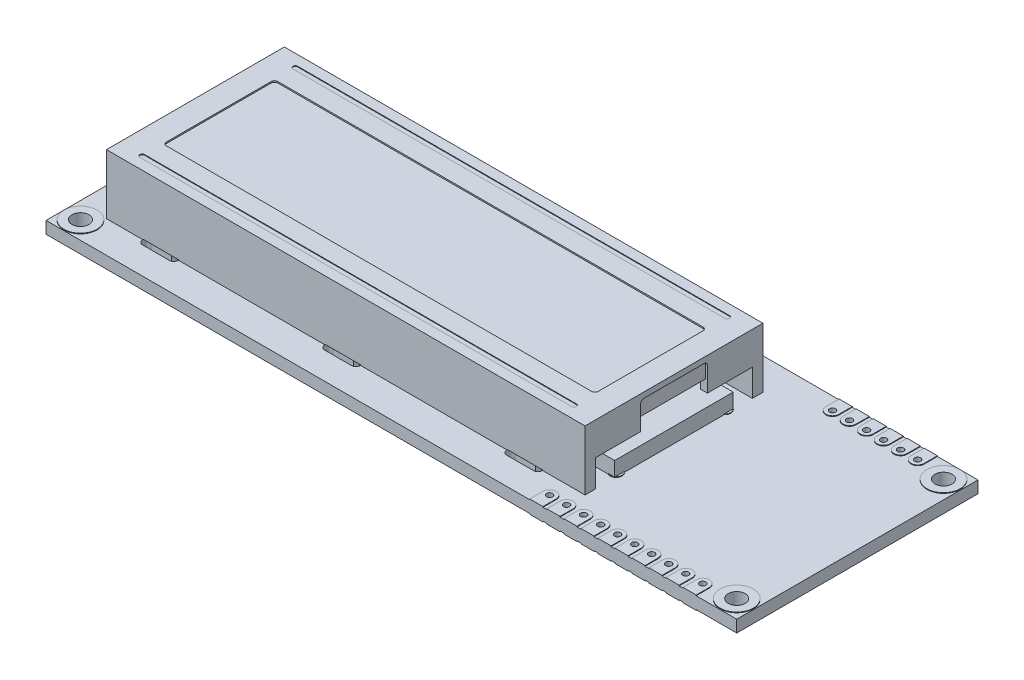
SolidWorks part; units mm, degrees
ref_plane "Front Plane" through (0, 0, 0) normal (0, 0, 1) x (1, 0, 0)
ref_plane "Top Plane" through (0, 0, 0) normal (0, 1, 0) x (1, 0, 0)
ref_plane "Right Plane" through (0, 0, 0) normal (1, 0, 0) x (0, 0, -1)
sketch "Sketch1" plane through (0, 0, 0) normal (0, 1, 0) x (1, 0, 0)
  line L5 (4.2965, 31.2697) -> (75.7035, 31.2697)
  line L6 (4.2965, 31.2697) -> (4.2965, 4.7303)
  line L7 (4.2965, 4.7303) -> (75.7035, 4.7303)
  line L8 (75.7035, 31.2697) -> (75.7035, 4.7303)
  line L9 (4.2965, 31.2697) -> (75.7035, 4.7303) construction
  line L10 (4.2965, 4.7303) -> (75.7035, 31.2697) construction
  point P5 (40, 18)
  dimension "D1" = 71.407
extrude "Boss-Extrude2" add sketch "Sketch1" along normal blind 8.93 from offset 1.79
sketch "Sketch3" plane through (0, 0, 0) normal (0, 1, 0) x (1, 0, 0)
  line L3 (40, 36) -> (103.07, 36)
  line L5 (0, 0) -> (103.07, 0)
  line L6 (0, 0) -> (0, 36)
  line L7 (0, 36) -> (103.07, 36)
  line L8 (103.07, 0) -> (103.07, 36)
  line L9 (0, 0) -> (103.07, 36) construction
  line L10 (0, 36) -> (103.07, 0) construction
  dimension "D1" = 103.07
extrude "Boss-Extrude3" add sketch "Sketch3" along normal blind 1.79 contours L5 L8 L3 L7 L6 region at (51.535, 0, -18)
sketch "Sketch4" plane through (0, 0, 0) normal (0, 1, 0) x (1, 0, 0)
  line L5 (7.78, 9.685) -> (72.22, 9.685)
  line L6 (7.78, 9.685) -> (7.78, 26.315)
  line L7 (7.78, 26.315) -> (72.22, 26.315)
  line L8 (72.22, 9.685) -> (72.22, 26.315)
  line L9 (7.78, 9.685) -> (72.22, 26.315) construction
  line L10 (7.78, 26.315) -> (72.22, 9.685) construction
extrude "Cut-Extrude1" cut sketch "Sketch4" against normal blind 0.2 from surface starting at face at (40, 10.72, -18)
ref_plane "Plane1" through (0, 10.72, 0) normal (0, 1, 0) x (1, 0, 0)
sketch "Sketch6" plane through (0, 10.72, 0) normal (0, 1, 0) x (1, 0, 0)
  line L4 (7.78, 29.7697) -> (72.22, 29.7697)
  line L5 (7.78, 29.0648) -> (72.22, 29.0648)
  circle A0 centre (7.78, 29.4173) radius 0.3524
  circle A1 centre (72.22, 29.4173) radius 0.3524
extrude "Cut-Extrude4" cut sketch "Sketch6" against normal blind 0.1 contours A1 L4 A0 L5 | A1 | A0 region at (40, 10.72, -29.4173) region at (7.78, 10.72, -29.4173) region at (72.22, 10.72, -29.4173)
ref_plane "Plane2" through (0, 0, -18) normal (0, 0, 1) x (1, 0, 0)
mirror "Mirror1" about plane through (0, 0, -18) normal (0, 0, 1) of "Cut-Extrude4"
fillet "Fillet1" radius 0.5 4 edges at (72.22, 10.62, -9.685) (72.22, 10.62, -26.315) (7.78, 10.62, -9.685) (7.78, 10.62, -26.315)
sketch "Sketch7" plane through (0, 0, 0) normal (1, 0, 0) x (0, 0, -1)
  line L5 (6.3, 1.79) -> (29.7, 1.79)
  line L6 (6.3, 1.79) -> (6.3, 5.83)
  line L7 (6.3, 5.83) -> (29.7, 5.83)
  line L8 (29.7, 1.79) -> (29.7, 5.83)
  line L9 (6.3, 1.79) -> (29.7, 5.83) construction
  line L10 (6.3, 5.83) -> (29.7, 1.79) construction
  point P6 (18, 3.81)
extrude "Cut-Extrude5" cut sketch "Sketch7" along normal through all contours L5 L8 L7 L6 region at (0, 3.81, -18)
ref_plane "Plane3" through (4.2965, 0, 0) normal (-1, 0, 0) x (0, 0, 1)
sketch "Sketch8" plane through (4.2965, 0, 0) normal (-1, 0, 0) x (0, 0, 1)
  line L2 (0, 1.79) -> (-36, 1.79) construction
  line L6 (-26.84, 1.79) -> (-9.155, 1.79)
  line L7 (-26.84, 1.79) -> (-26.84, 4.04)
  line L8 (-26.84, 4.04) -> (-9.155, 4.04)
  line L9 (-9.155, 1.79) -> (-9.155, 4.04)
extrude "Boss-Extrude5" add sketch "Sketch8" against normal blind 69.41 from offset 2 offset against normal yes
sketch "Sketch13" plane through (0, 4.04, 0) normal (0, 1, 0) x (1, 0, 0)
  line L0 (6.2965, 26.84) -> (6.2965, 9.155)
  line L2 (1.5, 20.9275) -> (6.2965, 26.84)
  line L5 (1.5, 20.9275) -> (1.5, 15.0675)
  line L8 (1.5, 15.0675) -> (6.2965, 9.155)
extrude "Boss-Extrude6" add sketch "Sketch13" against normal up to next
ref_plane "Plane5" through (75.7035, 0, 0) normal (1, 0, 0) x (0, 0, -1)
sketch "Sketch14" plane through (75.7035, 0, 0) normal (1, 0, 0) x (0, 0, -1)
  line L2 (18, 6.996) -> (18, -6.996) construction
  line L3 (18, 9.9) -> (13.02, 9.9)
  line L4 (18, 9.9) -> (22.98, 9.9)
  line L6 (13.02, 9.9) -> (22.98, 9.9)
  line L7 (13.02, 9.9) -> (13.02, 5.83)
  line L8 (13.02, 5.83) -> (22.98, 5.83)
  line L9 (22.98, 9.9) -> (22.98, 5.83)
extrude "Cut-Extrude6" cut sketch "Sketch14" against normal blind 0.3 contours L9 L4 L3 L7 L8 region at (75.7035, 7.865, -18)
fillet "Fillet2" radius 0.5 2 edges at (75.5535, 9.9, -22.98) (75.5535, 9.9, -13.02)
sketch "Sketch15" plane through (75.4035, 0, 0) normal (1, 0, 0) x (0, 0, -1)
  line L1 (13.02, 9.4) -> (13.02, 5.83) construction
  line L3 (13.02, 7.5) -> (22.98, 7.5)
  line L4 (13.02, 7.5) -> (13.02, 5.83)
  line L5 (13.02, 5.83) -> (22.98, 5.83)
  line L6 (22.98, 7.5) -> (22.98, 5.83)
extrude "Cut-Extrude7" cut sketch "Sketch15" against normal blind 70.4
sketch "Sketch18" plane through (75.7035, 0, 0) normal (1, 0, 0) x (0, 0, -1)
  line L2 (13.02, 9.4) -> (13.02, 5.83) construction
  line L3 (6.3, 7.5) -> (13.02, 7.5)
  line L4 (6.3, 7.5) -> (6.3, 5.83)
  line L5 (6.3, 5.83) -> (13.02, 5.83)
  line L6 (13.02, 7.5) -> (13.02, 5.83)
  line L7 (6.3, 5.83) -> (13.02, 5.83) construction
  line L8 (22.98, 5.83) -> (29.7, 5.83) construction
  line L9 (29.7, 7.5) -> (22.98, 7.5)
  line L10 (29.7, 7.5) -> (29.7, 5.83)
  line L11 (29.7, 5.83) -> (22.98, 5.83)
  line L12 (22.98, 7.5) -> (22.98, 5.83)
  line L13 (22.98, 9.4) -> (22.98, 5.83) construction
extrude "Cut-Extrude8" cut sketch "Sketch18" against normal blind 68.4 from offset 1 offset against normal yes
sketch "Sketch20" plane through (0, 0, 0) normal (0, 1, 0) x (1, 0, 0)
  circle A0 centre (2.57, 33.43) radius 2.475
  circle A1 centre (100.4939, 33.43) radius 2.475
  circle A2 centre (2.57, 2.57) radius 2.475
  circle A3 centre (100.4939, 2.57) radius 2.475
extrude "Boss-Extrude7" add sketch "Sketch20" along normal blind 1.99 from offset 0.1 offset against normal yes
sketch "Sketch23" plane through (0, 0, 0) normal (0, 1, 0) x (1, 0, 0)
  circle A0 centre (2.57, 33.43) radius 1.27
  circle A1 centre (100.4939, 33.43) radius 1.27
  circle A2 centre (2.57, 2.57) radius 1.27
  circle A3 centre (100.4939, 2.57) radius 1.27
extrude "Cut-Extrude10" cut sketch "Sketch23" against normal through all both and the other way through all
sketch "Sketch24" plane through (0, 0, 0) normal (0, 1, 0) x (1, 0, 0)
  line L0 (103.07, 0) -> (75.11, 0)
  line L4 (1.5, 15.0675) -> (1.5, 20.9275) construction
  line L5 (103.07, 0) -> (103.07, 36) construction
  line L6 (0, 0) -> (103.07, 0) construction
  line L9 (0.3, 16.1022) -> (1.5, 16.1022)
  line L10 (0.3, 16.1022) -> (0.3, 17.3067)
  line L11 (0.3, 17.3067) -> (1.5, 17.3067)
  line L12 (1.5, 16.1022) -> (1.5, 17.3067)
  line L13 (0.3, 16.1022) -> (1.5, 17.3067) construction
  line L14 (0.3, 17.3067) -> (1.5, 16.1022) construction
  circle A0 centre (0.9, 10.6) radius 0.9
  circle A1 centre (0.9, 14.2) radius 0.9
  circle A2 centre (0.9, 25.72) radius 0.9
  circle A3 centre (0.9, 21.88) radius 0.9
  circle A4 centre (0.9, 19.2833) radius 0.6
  circle A5 centre (4.85, 26.17) radius 0.9
  circle A6 centre (4.85, 9.95) radius 0.9
  circle A7 centre (75.11, 9.95) radius 0.9
  circle A8 centre (75.11, 26.17) radius 0.9
  point P22 (0.9, 16.7044)
extrude "Boss-Extrude16" add sketch "Sketch24" along normal blind 1.99 from offset 0.1 separate body contours A3 | A4 | L9 L12 L11 L10 | A1 | A6 | A0 | A7 | A8 | A2 | A5 region at (0.9, 0, -16.7044) region at (0.9, 0, -10.6) region at (0.9, 0, -14.2) region at (0.9, 0, -25.72) region at (0.9, 0, -21.88) region at (0.9, 0, -19.2833) region at (4.85, 0, -26.17) region at (4.85, 0, -9.95) region at (75.11, 0, -9.95) region at (75.11, 0, -26.17) offset against normal yes
sketch "Sketch26" plane through (0, 0, 0) normal (0, 1, 0) x (1, 0, 0)
  circle A0 centre (0.9, 25.72) radius 0.54
  circle A1 centre (0.9, 21.88) radius 0.54
  circle A2 centre (0.9, 19.2833) radius 0.45
  circle A3 centre (0.9, 16.7044) radius 0.45
  circle A4 centre (0.9, 14.2) radius 0.54
  circle A5 centre (0.9, 10.6) radius 0.54
  circle A7 centre (4.85, 9.95) radius 0.54
  circle A9 centre (4.85, 26.17) radius 0.54
  circle A11 centre (75.11, 26.17) radius 0.54
  circle A13 centre (75.11, 9.95) radius 0.54
extrude "Cut-Extrude11" cut sketch "Sketch26" along normal blind 1.99 from offset 0.1 contours A0 | A9 | A1 | A2 | A4 | A5 | A7 | A13 | A3 | A11 region at (0.9, 0, -25.72) region at (0.9, 0, -21.88) region at (0.9, 0, -19.2833) region at (0.9, 0, -14.2) region at (0.9, 0, -10.6) region at (4.85, 0, -9.95) region at (4.85, 0, -26.17) region at (75.11, 0, -9.95) offset against normal yes
sketch "Sketch27" plane through (0, 0, 0) normal (0, 1, 0) x (1, 0, 0)
  line L0 (95.0478, 34.03) -> (95.0478, 36)
  line L2 (97.014, 0) -> (95.0478, 0)
  line L3 (95.0478, 0) -> (95.0478, 1.97)
  line L4 (0, 36) -> (103.07, 36) construction
  line L5 (97.014, 1.97) -> (97.014, 0)
  line L6 (92.5078, 0) -> (92.5078, 1.97)
  line L7 (94.474, 1.97) -> (94.474, 0)
  line L8 (94.474, 0) -> (92.5078, 0)
  line L9 (89.9678, 0) -> (89.9678, 1.97)
  line L10 (91.934, 1.97) -> (91.934, 0)
  line L11 (91.934, 0) -> (89.9678, 0)
  line L12 (87.4278, 0) -> (87.4278, 1.97)
  line L13 (89.394, 1.97) -> (89.394, 0)
  line L14 (89.394, 0) -> (87.4278, 0)
  line L15 (84.8878, 0) -> (84.8878, 1.97)
  line L16 (86.854, 1.97) -> (86.854, 0)
  line L17 (86.854, 0) -> (84.8878, 0)
  line L18 (82.3478, 0) -> (82.3478, 1.97)
  line L19 (84.314, 1.97) -> (84.314, 0)
  line L20 (84.314, 0) -> (82.3478, 0)
  line L21 (79.8078, 0) -> (79.8078, 1.97)
  line L22 (81.774, 1.97) -> (81.774, 0)
  line L23 (81.774, 0) -> (79.8078, 0)
  line L24 (77.2678, 0) -> (77.2678, 1.97)
  line L25 (79.234, 1.97) -> (79.234, 0)
  line L26 (79.234, 0) -> (77.2678, 0)
  line L27 (74.7278, 0) -> (74.7278, 1.97)
  line L28 (76.694, 1.97) -> (76.694, 0)
  line L29 (76.694, 0) -> (74.7278, 0)
  line L30 (72.1878, 0) -> (72.1878, 1.97)
  line L31 (74.154, 1.97) -> (74.154, 0)
  line L32 (74.154, 0) -> (72.1878, 0)
  line L33 (95.0478, 36) -> (97.014, 36)
  line L34 (97.014, 36) -> (97.014, 34.03)
  line L35 (95.0478, 34.03) -> (97.014, 34.03)
  line L39 (94.474, 36) -> (94.474, 34.03)
  line L40 (94.474, 36) -> (92.5078, 36)
  line L41 (92.5078, 36) -> (92.5078, 34.03)
  line L42 (91.934, 36) -> (91.934, 34.03)
  line L43 (91.934, 36) -> (89.9678, 36)
  line L44 (89.9678, 36) -> (89.9678, 34.03)
  line L45 (89.394, 36) -> (89.394, 34.03)
  line L46 (89.394, 36) -> (87.4278, 36)
  line L47 (87.4278, 36) -> (87.4278, 34.03)
  line L48 (86.854, 36) -> (86.854, 34.03)
  line L49 (86.854, 36) -> (84.8878, 36)
  line L50 (84.8878, 36) -> (84.8878, 34.03)
  line L51 (58.914, 1.97) -> (58.914, 0) [skipped]
  line L52 (56.9478, 0) -> (56.9478, 1.97) [skipped]
  line L53 (58.914, 0) -> (56.9478, 0) [skipped]
  line L54 (61.454, 1.97) -> (61.454, 0) [skipped]
  line L55 (59.4878, 0) -> (59.4878, 1.97) [skipped]
  line L56 (61.454, 0) -> (59.4878, 0) [skipped]
  line L57 (62.0278, 0) -> (62.0278, 1.97) [skipped]
  line L58 (63.994, 1.97) -> (63.994, 0) [skipped]
  line L59 (63.994, 0) -> (62.0278, 0) [skipped]
  line L60 (64.5678, 0) -> (64.5678, 1.97) [skipped]
  line L61 (66.534, 1.97) -> (66.534, 0) [skipped]
  line L62 (66.534, 0) -> (64.5678, 0) [skipped]
  line L63 (67.1078, 0) -> (67.1078, 1.97) [skipped]
  line L64 (69.074, 1.97) -> (69.074, 0) [skipped]
  line L65 (69.074, 0) -> (67.1078, 0) [skipped]
  line L66 (69.6478, 0) -> (69.6478, 1.97) [skipped]
  line L67 (71.614, 1.97) -> (71.614, 0) [skipped]
  line L68 (71.614, 0) -> (69.6478, 0) [skipped]
  line L69 (84.314, 36) -> (84.314, 34.03)
  line L70 (84.314, 36) -> (82.3478, 36)
  line L71 (82.3478, 36) -> (82.3478, 34.03)
  circle A0 centre (96.0309, 1.97) radius 0.9831
  circle A1 centre (93.4909, 1.97) radius 0.9831
  circle A2 centre (90.9509, 1.97) radius 0.9831
  circle A3 centre (88.4109, 1.97) radius 0.9831
  circle A4 centre (85.8709, 1.97) radius 0.9831
  circle A5 centre (83.3309, 1.97) radius 0.9831
  circle A6 centre (80.7909, 1.97) radius 0.9831
  circle A7 centre (78.2509, 1.97) radius 0.9831
  circle A8 centre (75.7109, 1.97) radius 0.9831
  circle A9 centre (73.1709, 1.97) radius 0.9831
  circle A10 centre (96.0309, 34.03) radius 0.9831
  circle A11 centre (93.4909, 34.03) radius 0.9831
  circle A12 centre (90.9509, 34.03) radius 0.9831
  circle A13 centre (88.4109, 34.03) radius 0.9831
  circle A14 centre (85.8709, 34.03) radius 0.9831
  circle A15 centre (83.3309, 34.03) radius 0.9831
  circle A16 centre (57.9309, 1.97) radius 0.9831 [skipped]
  circle A17 centre (60.4709, 1.97) radius 0.9831 [skipped]
  circle A18 centre (63.0109, 1.97) radius 0.9831 [skipped]
  circle A19 centre (65.5509, 1.97) radius 0.9831 [skipped]
  circle A20 centre (68.0909, 1.97) radius 0.9831 [skipped]
  circle A21 centre (70.6309, 1.97) radius 0.9831 [skipped]
  dimension "D1" = 16
extrude "Boss-Extrude17" add sketch "Sketch27" along normal blind 1.99 from offset 0.1 contours A15 | A14 | A14 | A13 | A13 | A12 | A12 | A11 | A9 L30 L32 L31 | A9 | A8 L27 L29 L28 | A8 | A7 L24 L26 L25 | A6 L21 L23 L22 | A6 | A5 | A5 L18 L20 L19 | A4 L15 L17 L16 | A3 L12 L14 L13 | A3 | A2 | A2 L9 L11 L10 | A1 L6 L8 L7 | A1 | A0 L3 L2 L5 | A7 | A10 L34 L33 L0 | A15 | A11 | A4 | A0 | A10 region at (96.0309, 0, -35.381) region at (96.0309, 0, -0.619) region at (93.4909, 0, -0.619) region at (93.4909, 0, -1.97) region at (90.9509, 0, -0.619) region at (90.9509, 0, -1.97) region at (88.4109, 0, -0.619) region at (88.4109, 0, -1.97) region at (85.8709, 0, -0.619) region at (83.3309, 0, -0.619) region at (83.3309, 0, -1.97) region at (80.7909, 0, -0.619) region at (80.7909, 0, -1.97) region at (78.2509, 0, -0.619) region at (78.2509, 0, -1.97) region at (75.7109, 0, -0.619) region at (75.7109, 0, -1.97) region at (73.1709, 0, -0.619) region at (73.1709, 0, -1.97) region at (93.4909, 0, -35.381) region at (90.9509, 0, -35.381) region at (90.9509, 0, -34.03) region at (88.4109, 0, -35.381) region at (88.4109, 0, -34.03) region at (85.8709, 0, -35.381) region at (85.8709, 0, -34.03) region at (83.3309, 0, -35.381) offset against normal yes
sketch "Sketch28" plane through (0, 0, 0) normal (0, 1, 0) x (1, 0, 0)
  circle A0 centre (93.4909, 1.97) radius 0.45
  circle A1 centre (96.0309, 1.97) radius 0.45
  circle A2 centre (90.9509, 1.97) radius 0.45
  circle A3 centre (88.4109, 1.97) radius 0.45
  circle A4 centre (85.8709, 1.97) radius 0.45
  circle A5 centre (83.3309, 1.97) radius 0.45
  circle A6 centre (80.7909, 1.97) radius 0.45
  circle A7 centre (78.2509, 1.97) radius 0.45
  circle A8 centre (75.7109, 1.97) radius 0.45
  circle A9 centre (73.1709, 1.97) radius 0.45
  circle A10 centre (96.0309, 34.03) radius 0.45
  circle A11 centre (93.4909, 34.03) radius 0.45
  circle A12 centre (90.9509, 34.03) radius 0.45
  circle A13 centre (88.4109, 34.03) radius 0.45
  circle A14 centre (85.8709, 34.03) radius 0.45
  circle A15 centre (83.3309, 34.03) radius 0.45
  circle A16 centre (70.6309, 1.97) radius 0.45 [skipped]
  circle A17 centre (68.0909, 1.97) radius 0.45 [skipped]
  circle A18 centre (65.5509, 1.97) radius 0.45 [skipped]
  circle A19 centre (63.0109, 1.97) radius 0.45 [skipped]
  circle A20 centre (60.4709, 1.97) radius 0.45 [skipped]
  circle A21 centre (57.9309, 1.97) radius 0.45 [skipped]
  point P33 (0, 0)
  dimension "D1" = 16
extrude "Cut-Extrude12" cut sketch "Sketch28" against normal through all both and the other way through all contours A8 | A7 | A6 | A5 | A4 | A3 | A2 | A0 | A1 | A15 | A14 | A12 | A11 | A10 | A9 | A13 region at (93.4909, 0, -1.97) region at (96.0309, 0, -1.97) region at (90.9509, 0, -1.97) region at (88.4109, 0, -1.97) region at (85.8709, 0, -1.97) region at (83.3309, 0, -1.97) region at (80.7909, 0, -1.97) region at (78.2509, 0, -1.97) region at (75.7109, 0, -1.97) region at (96.0309, 0, -34.03) region at (93.4909, 0, -34.03) region at (90.9509, 0, -34.03) region at (85.8709, 0, -34.03) region at (83.3309, 0, -34.03)
ref_plane "Plane6" through (0, 0, 0) normal (0, -1, 0) x (-1, 0, 0)
sketch "Sketch29" plane through (0, 0, 0) normal (0, -1, 0) x (-1, 0, 0)
  line L0 (-103.07, 36) -> (-69.36, 36)
  line L2 (-68.81, 27.3375) -> (-68.81, 25.7375)
  line L3 (-73.1, 23.05) -> (-74.7, 23.05)
  line L4 (-73.1, 23.05) -> (-73.1, 24.2)
  line L5 (-73.1, 24.2) -> (-74.7, 24.2)
  line L6 (-75.5, 23.05) -> (-77.1, 23.05)
  line L7 (-75.5, 23.05) -> (-75.5, 24.2)
  line L8 (-75.5, 24.2) -> (-77.1, 24.2)
  line L9 (-77.1, 23.05) -> (-77.1, 24.2)
  line L10 (-74.7, 23.05) -> (-74.7, 24.2)
  line L11 (-73.1, 21.1) -> (-74.7, 21.1)
  line L12 (-73.1, 21.1) -> (-73.1, 22.25)
  line L13 (-73.1, 22.25) -> (-74.7, 22.25)
  line L14 (-75.5, 21.1) -> (-77.1, 21.1)
  line L15 (-75.5, 21.1) -> (-75.5, 22.25)
  line L16 (-75.5, 22.25) -> (-77.1, 22.25)
  line L17 (-77.1, 21.1) -> (-77.1, 22.25)
  line L18 (-74.7, 21.1) -> (-74.7, 22.25)
  line L19 (-73.1, 19.15) -> (-74.7, 19.15)
  line L20 (-73.1, 19.15) -> (-73.1, 20.3)
  line L21 (-73.1, 20.3) -> (-74.7, 20.3)
  line L22 (-75.5, 19.15) -> (-77.1, 19.15)
  line L23 (-75.5, 19.15) -> (-75.5, 20.3)
  line L24 (-75.5, 20.3) -> (-77.1, 20.3)
  line L25 (-77.1, 19.15) -> (-77.1, 20.3)
  line L26 (-74.7, 19.15) -> (-74.7, 20.3)
  line L27 (-68.81, 27.3375) -> (-69.96, 27.3375)
  line L28 (-69.96, 27.3375) -> (-69.96, 25.7375)
  line L29 (-68.81, 24.9375) -> (-68.81, 23.3375)
  line L30 (-68.81, 24.9375) -> (-69.96, 24.9375)
  line L31 (-69.96, 24.9375) -> (-69.96, 23.3375)
  line L32 (-68.81, 23.3375) -> (-69.96, 23.3375)
  line L33 (-68.81, 25.7375) -> (-69.96, 25.7375)
  line L34 (0, 36) -> (-82.3478, 36) construction
  line L35 (-25.55, 21.62) -> (-27.15, 21.62)
  line L36 (-25.55, 21.62) -> (-25.55, 22.77)
  line L37 (-25.55, 22.77) -> (-27.15, 22.77)
  line L38 (-27.95, 21.62) -> (-29.55, 21.62)
  line L39 (-27.95, 21.62) -> (-27.95, 22.77)
  line L40 (-27.95, 22.77) -> (-29.55, 22.77)
  line L41 (-29.55, 21.62) -> (-29.55, 22.77)
  line L42 (-27.15, 21.62) -> (-27.15, 22.77)
  line L43 (-15.0314, 29.08) -> (-9.7371, 29.08)
  line L44 (-25.55, 19.67) -> (-27.15, 19.67)
  line L45 (-25.55, 19.67) -> (-25.55, 20.82)
  line L46 (-25.55, 20.82) -> (-27.15, 20.82)
  line L47 (-27.95, 19.67) -> (-29.55, 19.67)
  line L48 (-27.95, 19.67) -> (-27.95, 20.82)
  line L49 (-27.95, 20.82) -> (-29.55, 20.82)
  line L50 (-29.55, 19.67) -> (-29.55, 20.82)
  line L51 (-27.15, 19.67) -> (-27.15, 20.82)
  line L52 (-25.55, 17.72) -> (-27.15, 17.72)
  line L53 (-25.55, 17.72) -> (-25.55, 18.87)
  line L54 (-25.55, 18.87) -> (-27.15, 18.87)
  line L55 (-27.95, 17.72) -> (-29.55, 17.72)
  line L56 (-27.95, 17.72) -> (-27.95, 18.87)
  line L57 (-27.95, 18.87) -> (-29.55, 18.87)
  line L58 (-29.55, 17.72) -> (-29.55, 18.87)
  line L59 (-27.15, 17.72) -> (-27.15, 18.87)
  line L60 (-42.1957, 29.08) -> (-36.9014, 29.08)
  line L61 (-69.36, 29.08) -> (-64.0657, 29.08)
  line L62 (-69.36, 29.08) -> (-69.36, 30.4457)
  line L63 (-69.36, 30.4457) -> (-64.0657, 30.4457)
  line L64 (-64.0657, 29.08) -> (-64.0657, 30.4457)
  line L65 (-42.1957, 29.08) -> (-42.1957, 30.4457)
  line L66 (-42.1957, 30.4457) -> (-36.9014, 30.4457)
  line L67 (-36.9014, 29.08) -> (-36.9014, 30.4457)
  line L68 (-15.0314, 29.08) -> (-15.0314, 30.4457)
  line L69 (-15.0314, 30.4457) -> (-9.7371, 30.4457)
  line L70 (-9.7371, 29.08) -> (-9.7371, 30.4457)
  line L71 (-42.1957, 5.49) -> (-36.9014, 5.49)
  line L72 (-15.0314, 5.49) -> (-9.7371, 5.49)
  line L73 (-15.0314, 5.49) -> (-15.0314, 6.8557)
  line L74 (-15.0314, 6.8557) -> (-9.7371, 6.8557)
  line L75 (-9.7371, 5.49) -> (-9.7371, 6.8557)
  line L76 (-7.27, 21.25) -> (-7.27, 22.95)
  line L77 (-7.27, 14.07) -> (-7.27, 15.77)
  line L78 (-74.13, 14.91) -> (-75.59, 14.91)
  line L79 (-74.13, 14.91) -> (-74.13, 16.12)
  line L80 (-76.19, 14.91) -> (-77.65, 14.91)
  line L81 (-76.19, 14.91) -> (-76.19, 16.12)
  line L82 (-76.19, 16.12) -> (-77.65, 16.12)
  line L83 (-77.65, 14.91) -> (-77.65, 16.12)
  line L84 (-74.13, 16.12) -> (-75.59, 16.12)
  line L85 (-75.59, 14.91) -> (-75.59, 16.12)
  line L86 (-12.2, 13) -> (-12.2, 14.7)
  line L87 (-12.2, 13) -> (-14.2, 13)
  line L88 (-14.2, 13) -> (-14.2, 14.7)
  line L89 (-14.2, 14.7) -> (-12.2, 14.7)
  line L90 (-7.27, 14.07) -> (-9.27, 14.07)
  line L91 (-12.2, 16.2) -> (-12.2, 17.9)
  line L92 (-12.2, 16.2) -> (-14.2, 16.2)
  line L93 (-14.2, 16.2) -> (-14.2, 17.9)
  line L94 (-14.2, 17.9) -> (-12.2, 17.9)
  line L95 (-9.27, 14.07) -> (-9.27, 15.77)
  line L96 (-9.27, 15.77) -> (-7.27, 15.77)
  line L97 (-7.27, 17.27) -> (-7.27, 18.97)
  line L98 (-7.27, 17.27) -> (-9.27, 17.27)
  line L99 (-9.27, 17.27) -> (-9.27, 18.97)
  line L100 (-9.27, 18.97) -> (-7.27, 18.97)
  line L101 (-7.27, 21.25) -> (-9.27, 21.25)
  line L102 (-9.27, 21.25) -> (-9.27, 22.95)
  line L103 (-9.27, 22.95) -> (-7.27, 22.95)
  line L104 (-7.27, 24.45) -> (-7.27, 26.15)
  line L105 (-7.27, 24.45) -> (-9.27, 24.45)
  line L106 (-9.27, 24.45) -> (-9.27, 26.15)
  line L107 (-9.27, 26.15) -> (-7.27, 26.15)
  line L108 (-42.1957, 5.49) -> (-42.1957, 6.8557)
  line L109 (-42.1957, 6.8557) -> (-36.9014, 6.8557)
  line L110 (-36.9014, 5.49) -> (-36.9014, 6.8557)
  line L111 (-69.36, 5.49) -> (-64.0657, 5.49)
  line L112 (-69.36, 5.49) -> (-69.36, 6.8557)
  line L113 (-69.36, 6.8557) -> (-64.0657, 6.8557)
  line L114 (-64.0657, 5.49) -> (-64.0657, 6.8557)
  circle A0 centre (-4.85, 14.85) radius 0.99
  circle A1 centre (-4.85, 21.86) radius 0.99
extrude "Boss-Extrude18" add sketch "Sketch29" along normal blind 0.1 contours A0 | L96 L95 L90 L77 | L100 L99 L98 L97 | L94 L93 L92 L91 | L89 L88 L87 L86 | L103 L102 L101 L76 | L107 L106 L105 L104 | A1 | L43 L70 L69 L68 | L59 L52 L53 L54 | L51 L44 L45 L46 | L42 L35 L36 L37 | L41 L38 L39 L40 | L50 L47 L48 L49 | L58 L55 L56 L57 | L61 L64 L63 L62 | L33 L2 L27 L28 | L10 L3 L4 L5 | L9 L6 L7 L8 | L17 L14 L15 L16 | L18 L11 L12 L13 | L26 L19 L20 L21 | L25 L22 L23 L24 | L83 L80 L81 L82 | L111 L114 L113 L112 | L72 L75 L74 L73 | L60 L67 L66 L65 | L29 L32 L31 L30 | L85 L84 L79 L78 | L71 L110 L109 L108 region at (69.385, 0, -26.5375) region at (73.9, 0, -23.625) region at (76.3, 0, -23.625) region at (73.9, 0, -21.675) region at (76.3, 0, -21.675) region at (73.9, 0, -19.725) region at (76.3, 0, -19.725) region at (26.35, 0, -22.195) region at (28.75, 0, -22.195) region at (12.3843, 0, -29.7629) region at (26.35, 0, -20.245) region at (28.75, 0, -20.245) region at (26.35, 0, -18.295) region at (28.75, 0, -18.295) region at (66.7129, 0, -29.7629) region at (8.27, 0, -22.1) region at (8.27, 0, -14.92) region at (76.92, 0, -15.515) region at (13.2, 0, -13.85) region at (13.2, 0, -17.05) region at (8.27, 0, -18.12) region at (8.27, 0, -25.3) region at (66.7129, 0, -6.1729) region at (4.85, 0, -14.85) region at (4.85, 0, -21.86)
sketch "Sketch30" plane through (0, 0, 0) normal (0, -1, 0) x (-1, 0, 0)
  circle A0 centre (-4.85, 14.85) radius 0.375
  circle A1 centre (-4.85, 21.86) radius 0.375
extrude "Cut-Extrude13" cut sketch "Sketch30" against normal blind 1.97 from offset 0.1 contours A1 | A0 region at (4.85, 0, -21.86)
sketch "Sketch31" plane through (0, -0.1, 0) normal (0, -1, 0) x (-1, 0, 0)
  line L0 (-10.3623, 5.2851) -> (-14.4063, 5.2851)
  line L1 (-37.5266, 31.9009) -> (-41.5706, 31.9009)
  line L2 (-10.3623, 4.0349) -> (-14.4063, 4.0349)
  line L3 (-37.5266, 30.6506) -> (-41.5706, 30.6506)
  line L5 (-64.6909, 5.2851) -> (-68.7349, 5.2851)
  line L6 (-10.3623, 31.9009) -> (-14.4063, 31.9009)
  line L7 (-10.3623, 30.6506) -> (-14.4063, 30.6506)
  line L8 (-64.6909, 31.9009) -> (-68.7349, 31.9009)
  line L9 (-64.6909, 30.6506) -> (-68.7349, 30.6506)
  line L10 (-37.5266, 5.2851) -> (-41.5706, 5.2851)
  line L11 (-37.5266, 4.0349) -> (-41.5706, 4.0349)
  line L12 (-64.6909, 4.0349) -> (-68.7349, 4.0349)
  circle A0 centre (-10.3623, 4.66) radius 0.6251
  circle A1 centre (-14.4063, 4.66) radius 0.6251
  circle A2 centre (-10.3623, 31.2757) radius 0.6251
  circle A3 centre (-14.4063, 31.2757) radius 0.6251
  circle A4 centre (-37.5266, 31.2757) radius 0.6251
  circle A5 centre (-41.5706, 31.2757) radius 0.6251
  circle A6 centre (-64.6909, 31.2757) radius 0.6251
  circle A7 centre (-68.7349, 31.2757) radius 0.6251
  circle A8 centre (-37.5266, 4.66) radius 0.6251
  circle A9 centre (-41.5706, 4.66) radius 0.6251
  circle A10 centre (-64.6909, 4.66) radius 0.6251
  circle A11 centre (-68.7349, 4.66) radius 0.6251
extrude "Cut-Extrude14" cut sketch "Sketch31" against normal blind 1.97 contours A1 L2 A0 L0 | A0 | A1 | A3 L7 A2 L6 | A3 | A2 | A4 | A5 L3 A4 L1 | A5 | A6 | A7 L9 A6 L8 | A7 | A9 L11 A8 L10 | A8 | A9 | A11 L12 A10 L5 | A11 | A10 region at (12.3843, -0.1, -4.66) region at (10.3623, -0.1, -4.66) region at (14.4063, -0.1, -4.66) region at (39.5486, -0.1, -31.2757) region at (37.5266, -0.1, -31.2757) region at (41.5706, -0.1, -31.2757) region at (66.7129, -0.1, -4.66) region at (64.6909, -0.1, -4.66) region at (68.7349, -0.1, -4.66) region at (12.3843, -0.1, -31.2757) region at (10.3623, -0.1, -31.2757) region at (14.4063, -0.1, -31.2757) region at (66.7129, -0.1, -31.2757) region at (64.6909, -0.1, -31.2757) region at (68.7349, -0.1, -31.2757) region at (39.5486, -0.1, -4.66) region at (37.5266, -0.1, -4.66) region at (41.5706, -0.1, -4.66)
sketch "Sketch40" plane through (0, 0, -18) normal (0, 0, 1) x (1, 0, 0)
  line L0 (1.5, 2.915) -> (0.9, 2.915)
  line L1 (1.5, 1.79) -> (1.5, 4.04) construction
  line L2 (0.9, 2.915) -> (0.9, -0.1)
  line L3 (0.095, -0.1) -> (5.045, -0.1) construction
extrude "Extrude-Thin1" add sketch "Sketch40" along normal mid plane 0.75 from offset 1.29 thin thin type one direction wall 0.2
fillet "Fillet3" radius 0.2 1 edges at (0.7, 3.115, -16.71)
pattern_linear "LPattern1" count 2 spacing 2.58 along (0, 0, -1) of "Extrude-Thin1", "Fillet3"
sketch "Sketch41" plane through (0, 0, 0) normal (0, -1, 0) x (-1, 0, 0)
  line L0 (-41.5706, 30.772) -> (-41.1039, 31.2387)
  line L1 (-41.5706, 5.228) -> (-41.1039, 4.7613)
  line L2 (-41.1039, 4.7613) -> (-40.6372, 5.228)
  line L3 (-40.6372, 5.228) -> (-41.5706, 5.228)
  line L4 (-68.7349, 5.228) -> (-68.2682, 4.7613)
  line L5 (-41.1039, 31.2387) -> (-40.6372, 30.772)
  line L9 (-68.7349, 30.772) -> (-68.2682, 31.2387)
  line L10 (-68.2682, 31.2387) -> (-67.8015, 30.772)
  line L11 (-14.4063, 5.228) -> (-13.9396, 4.7613)
  line L12 (-13.9396, 4.7613) -> (-13.4729, 5.228)
  line L13 (-13.4729, 5.228) -> (-14.4063, 5.228)
  line L14 (-68.2682, 4.7613) -> (-67.8015, 5.228)
  line L15 (-40.6372, 30.772) -> (-41.5706, 30.772)
  line L16 (-14.4063, 30.772) -> (-13.9396, 31.2387)
  line L17 (-13.9396, 31.2387) -> (-13.4729, 30.772)
  line L18 (-41.5706, 5.228) -> (-41.0713, 5.228)
  line L19 (-13.4729, 30.772) -> (-14.4063, 30.772)
  line L20 (-67.8015, 30.772) -> (-68.7349, 30.772)
  line L26 (-67.8015, 5.228) -> (-68.7349, 5.228)
  line L28 (-14.4063, 30.772) -> (-13.907, 30.772)
extrude "Boss-Extrude19" add sketch "Sketch41" against normal blind 1.89 from offset 0.1 separate body contours L12 L13 L11 | L20 L10 L9 | L19 L17 L16 | L1 L2 L3 | L4 L14 L26 | L15 L0 L5 region at (68.2682, 0, -30.9276) region at (13.9396, 0, -5.0724) region at (13.9396, 0, -30.9276)
sketch "Sketch42" plane through (0, 0, 0) normal (0, -1, 0) x (-1, 0, 0)
  line L0 (-12.3843, 6.3166) -> (-13.9396, 4.7613)
  line L1 (-14.4063, 5.228) -> (-12.8509, 6.7833)
  line L2 (-12.8509, 6.7833) -> (-12.3843, 6.3166)
  line L3 (-13.9396, 4.7613) -> (-14.4063, 5.228)
  line L4 (-39.5466, 6.3166) -> (-41.1019, 4.7613)
  line L5 (-41.5686, 5.228) -> (-40.0132, 6.7833)
  line L6 (-40.0132, 6.7833) -> (-39.5466, 6.3166)
  line L7 (-41.1019, 4.7613) -> (-41.5686, 5.228)
  line L8 (-66.7128, 6.3166) -> (-68.2682, 4.7613)
  line L9 (-68.7349, 5.228) -> (-67.1795, 6.7833)
  line L10 (-67.1795, 6.7833) -> (-66.7128, 6.3166)
  line L11 (-68.2682, 4.7613) -> (-68.7349, 5.228)
  line L12 (-13.9396, 31.2387) -> (-12.384, 29.6831)
  line L13 (-13.9396, 31.2387) -> (-14.4063, 30.772)
  line L14 (-14.4063, 30.772) -> (-12.8509, 29.2167)
  line L15 (-12.8509, 29.2167) -> (-12.384, 29.6831)
  line L16 (-41.1019, 31.2387) -> (-39.5463, 29.6831)
  line L17 (-41.1019, 31.2387) -> (-41.5686, 30.772)
  line L18 (-41.5686, 30.772) -> (-40.0132, 29.2167)
  line L19 (-40.0132, 29.2167) -> (-39.5463, 29.6831)
  line L20 (-68.2682, 31.2387) -> (-66.7125, 29.6831)
  line L21 (-68.2682, 31.2387) -> (-68.7349, 30.772)
  line L22 (-68.7349, 30.772) -> (-67.1795, 29.2167)
  line L23 (-67.1795, 29.2167) -> (-66.7125, 29.6831)
extrude "Boss-Extrude20" add sketch "Sketch42" along normal blind 1.79 from offset 0.1
fillet "Fillet4" radius 0.2 12 edges at (12.6175, -1.89, -29.4499) (14.1729, -1.89, -31.0054) (39.7798, -1.89, -29.4499) (41.3352, -1.89, -31.0054) (66.946, -1.89, -29.4499) (68.5015, -1.89, -31.0054) (66.9462, -1.89, -6.55) (68.5015, -1.89, -4.9946) (41.3352, -1.89, -4.9946) (39.7799, -1.89, -6.55) (14.1729, -1.89, -4.9946) (12.6176, -1.89, -6.55)
sketch "Sketch43" plane through (0, -0.1, 0) normal (0, -1, 0) x (-1, 0, 0)
  line L0 (-73.1, 19.15) -> (-74.7, 19.15) construction
  line L1 (-73.9, 19.15) -> (-74.3989, 19.15)
  line L2 (-73.9, 19.15) -> (-73.9, 20.3)
  line L3 (-73.9, 20.3) -> (-74.3989, 20.3)
  line L4 (-74.3989, 19.15) -> (-74.3989, 20.3)
  line L5 (-73.1, 20.3) -> (-74.7, 20.3) construction
  line L6 (-75.5, 19.15) -> (-77.1, 19.15) construction
  line L7 (-76.3, 19.15) -> (-75.8041, 19.15)
  line L8 (-76.3, 19.15) -> (-76.3, 20.3)
  line L9 (-76.3, 20.3) -> (-75.8041, 20.3)
  line L10 (-75.8041, 19.15) -> (-75.8041, 20.3)
  line L11 (-75.5, 20.3) -> (-77.1, 20.3) construction
  line L12 (-73.9, 21.1036) -> (-74.3989, 21.1036)
  line L13 (-73.9, 21.1036) -> (-73.9, 22.2536)
  line L14 (-73.9, 22.2536) -> (-74.3989, 22.2536)
  line L15 (-74.3989, 21.1036) -> (-74.3989, 22.2536)
  line L16 (-76.3, 21.1036) -> (-75.8041, 21.1036)
  line L17 (-76.3, 21.1036) -> (-76.3, 22.2536)
  line L18 (-76.3, 22.2536) -> (-75.8041, 22.2536)
  line L19 (-75.8041, 21.1036) -> (-75.8041, 22.2536)
  line L20 (-73.9, 23.0452) -> (-74.3989, 23.0452)
  line L21 (-73.9, 23.0452) -> (-73.9, 24.1952)
  line L22 (-73.9, 24.1952) -> (-74.3989, 24.1952)
  line L23 (-74.3989, 23.0452) -> (-74.3989, 24.1952)
  line L24 (-76.3, 23.0452) -> (-75.8041, 23.0452)
  line L25 (-76.3, 23.0452) -> (-76.3, 24.1952)
  line L26 (-76.3, 24.1952) -> (-75.8041, 24.1952)
  line L27 (-75.8041, 23.0452) -> (-75.8041, 24.1952)
  line L28 (-26.3748, 17.72) -> (-26.8737, 17.72)
  line L29 (-26.3748, 17.72) -> (-26.3748, 18.87)
  line L30 (-26.3748, 18.87) -> (-26.8737, 18.87)
  line L31 (-26.8737, 17.72) -> (-26.8737, 18.87)
  line L32 (-28.7748, 17.72) -> (-28.2789, 17.72)
  line L33 (-28.7748, 17.72) -> (-28.7748, 18.87)
  line L34 (-28.7748, 18.87) -> (-28.2789, 18.87)
  line L35 (-28.2789, 17.72) -> (-28.2789, 18.87)
  line L36 (-26.35, 19.67) -> (-26.8489, 19.67)
  line L37 (-26.35, 19.67) -> (-26.35, 20.82)
  line L38 (-26.35, 20.82) -> (-26.8489, 20.82)
  line L39 (-26.8489, 19.67) -> (-26.8489, 20.82)
  line L40 (-28.75, 19.67) -> (-28.2541, 19.67)
  line L41 (-28.75, 19.67) -> (-28.75, 20.82)
  line L42 (-28.75, 20.82) -> (-28.2541, 20.82)
  line L43 (-28.2541, 19.67) -> (-28.2541, 20.82)
  line L44 (-26.35, 21.62) -> (-26.8489, 21.62)
  line L45 (-26.35, 21.62) -> (-26.35, 22.77)
  line L46 (-26.35, 22.77) -> (-26.8489, 22.77)
  line L47 (-26.8489, 21.62) -> (-26.8489, 22.77)
  line L48 (-28.75, 21.62) -> (-28.2541, 21.62)
  line L49 (-28.75, 21.62) -> (-28.75, 22.77)
  line L50 (-28.75, 22.77) -> (-28.2541, 22.77)
  line L51 (-28.2541, 21.62) -> (-28.2541, 22.77)
extrude "Boss-Extrude21" add sketch "Sketch43" along normal blind 1
sketch "Sketch44" plane through (0, 0, 0) normal (0, -1, 0) x (-1, 0, 0)
  line L0 (-74.3989, 22.2593) -> (-75.8041, 22.2593)
  line L1 (-74.3989, 24.2026) -> (-75.8041, 24.2026)
  line L2 (-74.3989, 24.2026) -> (-74.3989, 23.0377)
  line L3 (-26.8489, 20.8275) -> (-28.2541, 20.8275)
  line L4 (-26.8489, 20.8275) -> (-26.8489, 19.6625)
  line L5 (-26.8489, 19.6625) -> (-28.2541, 19.6625)
  line L6 (-26.8489, 22.7775) -> (-28.2541, 22.7775)
  line L7 (-28.2541, 20.8275) -> (-28.2541, 19.6625)
  line L8 (-26.8489, 20.8275) -> (-28.2541, 19.6625) construction
  line L9 (-74.3989, 22.2593) -> (-74.3989, 21.0943)
  line L10 (-74.3989, 20.3075) -> (-75.8041, 20.3075)
  line L11 (-74.3989, 20.3075) -> (-74.3989, 19.1425)
  line L12 (-74.3989, 19.1425) -> (-75.8041, 19.1425)
  line L13 (-75.8041, 20.3075) -> (-75.8041, 19.1425)
  line L14 (-74.3989, 20.3075) -> (-75.8041, 19.1425) construction
  line L15 (-74.3989, 19.1425) -> (-75.8041, 20.3075) construction
  line L16 (-74.3989, 21.0943) -> (-75.8041, 21.0943)
  line L17 (-75.8041, 22.2593) -> (-75.8041, 21.0943)
  line L18 (-74.3989, 22.2593) -> (-75.8041, 21.0943) construction
  line L19 (-74.3989, 21.0943) -> (-75.8041, 22.2593) construction
  line L20 (-74.3989, 23.0377) -> (-75.8041, 23.0377)
  line L21 (-75.8041, 24.2026) -> (-75.8041, 23.0377)
  line L22 (-74.3989, 24.2026) -> (-75.8041, 23.0377) construction
  line L23 (-74.3989, 23.0377) -> (-75.8041, 24.2026) construction
  line L24 (-26.8489, 22.7775) -> (-26.8489, 21.6125)
  line L25 (-26.8489, 21.6125) -> (-28.2541, 21.6125)
  line L31 (-26.8737, 18.8775) -> (-28.2789, 18.8775)
  line L32 (-26.8737, 18.8775) -> (-26.8737, 17.7125)
  line L33 (-26.8737, 17.7125) -> (-28.2789, 17.7125)
  line L34 (-28.2789, 18.8775) -> (-28.2789, 17.7125)
  line L35 (-26.8737, 18.8775) -> (-28.2789, 17.7125) construction
  line L36 (-26.8737, 17.7125) -> (-28.2789, 18.8775) construction
  line L37 (-26.8489, 19.6625) -> (-28.2541, 20.8275) construction
  line L38 (-28.2541, 22.7775) -> (-28.2541, 21.6125)
  line L39 (-26.8489, 22.7775) -> (-28.2541, 21.6125) construction
  line L40 (-26.8489, 21.6125) -> (-28.2541, 22.7775) construction
  point P18 (-75.1015, 19.725)
extrude "Boss-Extrude22" add sketch "Sketch44" along normal blind 1.2
sketch "Sketch45" plane through (0, 0, 0) normal (0, -1, 0) x (-1, 0, 0)
  line L0 (-7.27, 21.25) -> (-7.27, 22.95) construction
  line L1 (-7.27, 22.1) -> (-9.27, 22.1)
  line L2 (-7.27, 22.1) -> (-7.27, 22.3069)
  line L3 (-7.27, 22.3069) -> (-9.27, 22.3069)
  line L4 (-9.27, 22.1) -> (-9.27, 22.3069)
  line L5 (-9.27, 21.25) -> (-9.27, 22.95) construction
  line L7 (-7.27, 25.0931) -> (-9.27, 25.0931)
  line L8 (-7.27, 25.0931) -> (-7.27, 25.3)
  line L9 (-7.27, 25.3) -> (-9.27, 25.3)
  line L10 (-9.27, 25.0931) -> (-9.27, 25.3)
extrude "Boss-Extrude23" add sketch "Sketch45" along normal blind 1
sketch "Sketch47" plane through (0, 0, 0) normal (0, -1, 0) x (-1, 0, 0)
  line L4 (-7.2526, 25.0931) -> (-9.2874, 25.0931)
  line L5 (-7.2526, 25.0931) -> (-7.2526, 22.3069)
  line L6 (-7.2526, 22.3069) -> (-9.2874, 22.3069)
  line L7 (-9.2874, 25.0931) -> (-9.2874, 22.3069)
  line L8 (-7.2526, 25.0931) -> (-9.2874, 22.3069) construction
  line L9 (-7.2526, 22.3069) -> (-9.2874, 25.0931) construction
  point P6 (-8.27, 23.7)
extrude "Boss-Extrude24" add sketch "Sketch47" along normal blind 1.1
sketch "Sketch48" plane through (0, 0, 0) normal (0, -1, 0) x (-1, 0, 0)
  circle A0 centre (-20, 19.25) radius 5.25
  circle A1 centre (-57.6, 19.25) radius 6.5
extrude "Boss-Extrude25" add sketch "Sketch48" along normal blind 2
fillet "Fillet5" radius 7.49 1 edges at (20, -2, -24.5)
fillet "Fillet6" radius 11 1 edges at (57.6, -2, -25.75)
